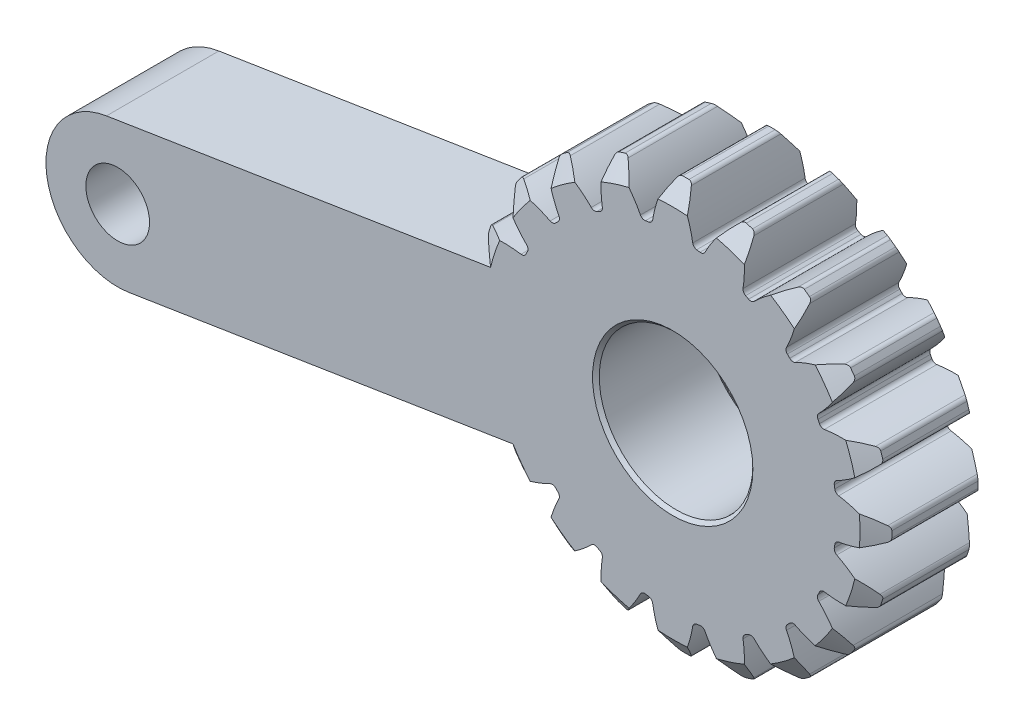
SolidWorks part; units mm, degrees
ref_plane "前视基准面" through (0, 0, 0) normal (0, 0, 1) x (1, 0, 0)
ref_plane "上视基准面" through (0, 0, 0) normal (0, 1, 0) x (1, 0, 0)
ref_plane "右视基准面" through (0, 0, 0) normal (1, 0, 0) x (0, 0, -1)
sketch "草图1" plane through (0, 0, 0) normal (1, 0, 0) x (0, 0, -1)
  line L0 (0, 0) -> (10, 0) construction
  line L1 (0, 4) -> (10, 4)
  line L4 (10, 4) -> (10, 11)
  line L5 (10, 11) -> (0, 11)
  line L6 (0, 11) -> (0, 4)
  line L7 (0, 0) -> (-1, 0) construction
  line L8 (-1, 0) -> (-1, -20) construction
  dimension "P" = 8
  dimension "B" = 10
  dimension "M" = 1
  dimension "Z" = 20
  dimension "D" = 22
sketch "草图2" plane through (0, 0, 0) normal (0, 0, 1) x (1, 0, 0)
  line L0 (0, 4) -> (0, 8) construction
  circle A0 centre (0, 0) radius 4
  circle A3 centre (0, 0) radius 6
  point P6 (0, 6)
  dimension "(D1)" = 4
sketch "草图11" plane through (-11.8785, -4, 0) normal (0, 0, 1) x (1, 0, 0)
  line L0 (11.8785, 4) -> (22.8785, 4) construction
  line L1 (21.8477, 3.2154) -> (11.8785, 4) construction
  circle A0 centre (11.8785, 4) radius 8.75
  arc A1 (20.5595, 2.9033) -> (20.6285, 4) centre (11.8785, 4) ccw construction
  arc A2 (21.8477, 3.2154) -> (21.8785, 4) centre (11.8785, 4) ccw construction
  arc A3 (22.874, 3.6859) -> (22.874, 4.3141) centre (11.8785, 4) ccw construction
  arc A4 (20.5595, 2.9033) -> (22.874, 3.6859) centre (19.7054, 9.2435) ccw construction
  point P1 (31.8785, 4)
  point P7 (11.8785, 5)
  point P13 (21.8477, 3.2154)
  point P17 (22.874, 4.3141)
  point P18 (20.5595, 5.0967)
  dimension "D1" = 22
  dimension "D" = 20
  dimension "D2" = 17.5
  dimension "m" = 1
  dimension "z" = 20
  dimension "D3" = 4.5
  dimension "D4" = 0.6283
  dimension "D5" = 2.1991
extrude "拉伸-齿轮a" add sketch "草图11" against normal blind 6
sketch "草图3" plane through (-1.3611, -4, 0) normal (0, 0, 1) x (1, 0, 0)
  line L1 (1.3611, 4) -> (12.3611, 4) construction
  line L2 (10.1111, 4) -> (12.3611, 4) construction
  circle A2 centre (1.3611, 4) radius 8.75 construction
  arc A3 (10.0421, 2.9033) -> (12.3566, 3.6859) centre (9.188, 9.2435) ccw construction
  arc A4 (12.3566, 3.6859) -> (12.3566, 4.3141) centre (1.3611, 4) ccw construction
  arc A5 (10.0421, 2.9033) -> (10.0421, 5.0967) centre (1.3611, 4) ccw
  arc A6 (10.0421, 2.9033) -> (12.3566, 3.6859) centre (9.188, 9.2435) ccw
  arc A7 (12.3566, 3.6859) -> (12.3566, 4.3141) centre (1.3611, 4) ccw
  arc A8 (10.0421, 5.0967) -> (12.3566, 4.3141) centre (9.188, -1.2435) cw
extrude "拉伸-齿轮b" add sketch "草图3" along normal up to surface (-6 mm away) up to face at (8.75, 0, -6)
fillet "圆角-齿轮" radius 0.25 4 edges at (10.9955, -0.3141, -3) (10.9955, 0.3141, -3) (8.681, -1.0967, -3) (8.681, 1.0967, -3)
pattern_circular "阵列-齿轮" count 20 over 360 about axis through (0, 0, -6) along (0, 0, 1) of "拉伸-齿轮b", "圆角-齿轮"
sketch "草图4" plane through (0, 0, -6) normal (0, 0, -1) x (-1, 0, 0)
  line L0 (-10, 0) -> (-12, 0) construction
  circle A0 centre (0, 0) radius 12
  circle A1 centre (0, 0) radius 10
extrude "切除-齿轮" cut sketch "草图4" against normal blind 1 draft 55
extrude "切除-拉伸2" cut sketch "草图4<2>" along normal blind 1 draft 55 from vertex starting at point (0, 4, 0)
sketch "草图4<2>" plane through (0, 0, -6) normal (0, 0, -1) x (-1, 0, 0) same geometry as "草图4"
sketch "草图13" plane through (0, 0, 0) normal (0, 0, 1) x (1, 0, 0)
  circle A0 centre (0, 0) radius 4.1
  dimension "D1" = 8.2
extrude "切除-拉伸4" cut sketch "草图13" against normal through all
chamfer "倒角1" distance 0.18 angle 45 2 edges at (4.1, 0, -6) (4.1, 0, 0)
sketch "草图14" plane through (0, 0, 0) normal (1, 0, 0) x (0, 0, -1)
  line L0 (0, 0) -> (10, 0) construction
  line L1 (0, 6) -> (0, -6) construction
  line L2 (12.5, 6.05) -> (7.5, 6.05)
  line L3 (12.5, 6.05) -> (12.5, 6)
  line L4 (12.5, 6) -> (7.5, 6)
  line L5 (7.5, 6.05) -> (7.5, 6)
  line L6 (2.5, 6.05) -> (-2.5, 6.05)
  line L7 (2.5, 6.05) -> (2.5, 6)
  line L8 (2.5, 6) -> (-2.5, 6)
  line L9 (-2.5, 6.05) -> (-2.5, 6)
  line L10 (10, 4) -> (10, 11) construction
  line L11 (7.5, 6) -> (2.5, 6) construction
  point P12 (0, 6)
  point P16 (10, 6)
  dimension "D1" = 0.05
sketch "草图15" plane through (0, 0, 0) normal (0, 0, 1) x (1, 0, 0)
  line L0 (-8.3535, -5.2) -> (-29.0316, -8.4751)
  line L1 (-9.5516, 2.3641) -> (-4.693, -0.1468)
  line L2 (-30.2297, -0.911) -> (-9.5516, 2.3641)
  line L3 (-4.693, -0.1468) -> (-8.3535, -5.2)
  line L4 (-30, 0) -> (0, 0) construction
  arc A3 (-30.2297, -0.911) -> (-29.0316, -8.4751) centre (-29.6307, -4.693) ccw
  circle A4 centre (-29.6307, -4.693) radius 1.7
  dimension "D2" = 3.4
  dimension "D1" = 30
extrude "凸台-拉伸1" add sketch "草图15" against normal up to surface (6 mm away) up to face at (4.28, 0, -6)
